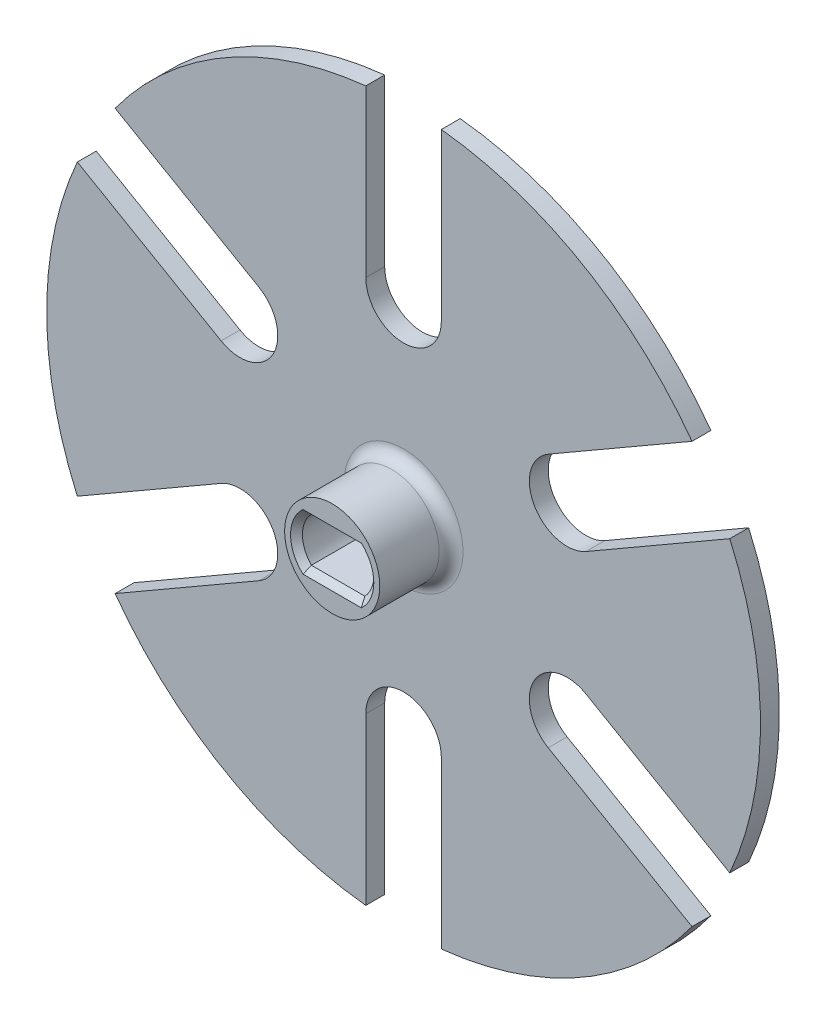
SolidWorks part; units mm, degrees
ref_plane "Front Plane" through (0, 0, 0) normal (0, 0, 1) x (1, 0, 0)
ref_plane "Top Plane" through (0, 0, 0) normal (0, 1, 0) x (1, 0, 0)
ref_plane "Right Plane" through (0, 0, 0) normal (1, 0, 0) x (0, 0, -1)
sketch "Sketch1" plane through (0, 0, 0) normal (0, 0, 1) x (1, 0, 0)
  line L0 (-2.25, 1.855) -> (2.25, 1.855)
  line L1 (-2.25, -1.855) -> (2.25, -1.855)
  line L2 (0, 1.855) -> (0, 0) construction
  line L3 (0, 0) -> (0, -1.855) construction
  arc A0 (-2.25, 1.855) -> (-2.25, -1.855) centre (-0.331, 0) ccw
  arc A1 (2.25, 1.855) -> (2.25, -1.855) centre (0.331, 0) cw
  circle A2 centre (0, 0) radius 4
  point P10 (-3, 0)
  point P11 (3, 0)
  dimension "D4" = 8
  dimension "D1" = 3.71
  dimension "D2" = 4.5
  dimension "D3" = 6
extrude "Boss-Extrude1" add sketch "Sketch1" along normal blind 6
sketch "Sketch2" plane through (0, 0, 0) normal (0, 0, -1) x (-1, 0, 0)
  circle A0 centre (0, 0) radius 30
  dimension "D1" = 60
extrude "Boss-Extrude2" add sketch "Sketch2" along normal blind 1.5875
sketch "Sketch3" plane through (0, 0, 0) normal (0, 0, 1) x (1, 0, 0)
  line L0 (0, 65.0875) -> (0, 14.2875) construction
  line L1 (1.5875, 65.0875) -> (1.5875, 14.2875)
  line L2 (-1.5875, 65.0875) -> (-1.5875, 14.2875)
  line L3 (0, 14.2875) -> (0, 0) construction
  arc A0 (1.5875, 65.0875) -> (-1.5875, 65.0875) centre (0, 65.0875) ccw
  arc A1 (-1.5875, 14.2875) -> (1.5875, 14.2875) centre (0, 14.2875) ccw
  point P2 (0, 39.6875)
  point P11 (0, 12.7)
  dimension "D3" = 3.175
  dimension "D1" = 12.7
  dimension "D2" = 50.8
extrude "Cut-Extrude1" [suppressed] cut sketch "Sketch3" against normal through all
pattern_circular "CirPattern1" [suppressed] count 10 over 360 of bodies 103
fillet "Fillet1" radius 1 1 edges at (4, 0, 0)
chamfer "Chamfer1" distance 0.5 angle 45 4 edges at (3, 0, 6) (0, -1.855, 6) (-3, 0, 6) (0, 1.855, 6)
sketch "Sketch4" plane through (0, 0, 0) normal (0, 0, 1) x (1, 0, 0)
  line L0 (0, 66.675) -> (0, 15.875) construction
  line L1 (3.175, 66.675) -> (3.175, 15.875)
  line L2 (-3.175, 66.675) -> (-3.175, 15.875)
  line L3 (0, 12.7) -> (0, 0) construction
  arc A0 (3.175, 66.675) -> (-3.175, 66.675) centre (0, 66.675) ccw
  arc A1 (-3.175, 15.875) -> (3.175, 15.875) centre (0, 15.875) ccw
  point P2 (0, 41.275)
  dimension "D1" = 6.35
  dimension "D2" = 12.7
  dimension "D3" = 50.8
extrude "Cut-Extrude2" cut sketch "Sketch4" against normal through all
pattern_circular "CirPattern2" count 6 over 360 about axis through (0, 0, -1.5875) along (0, 0, 1) of "Cut-Extrude2" reverse direction yes
sketch "Sketch5" [suppressed] plane through (0, 0, 0) normal (0, 0, 1) x (1, 0, 0)
  line L0 (0, 66.675) -> (0, 15.875) construction
  line L1 (3.175, 66.675) -> (3.175, 15.875)
  line L2 (-3.175, 66.675) -> (-3.175, 15.875)
  line L3 (0, 0) -> (0, 12.7) construction
  arc A0 (3.175, 66.675) -> (-3.175, 66.675) centre (0, 66.675) ccw
  arc A1 (-3.175, 15.875) -> (3.175, 15.875) centre (0, 15.875) ccw
  point P2 (0, 41.275)
  dimension "D3" = 50.8
  dimension "D1" = 12.7
  dimension "D2" = 6.35
extrude "Cut-Extrude3" [suppressed] cut sketch "Sketch5" against normal through all
pattern_circular "CirPattern3" [suppressed] count 5 over 360 of bodies 107
